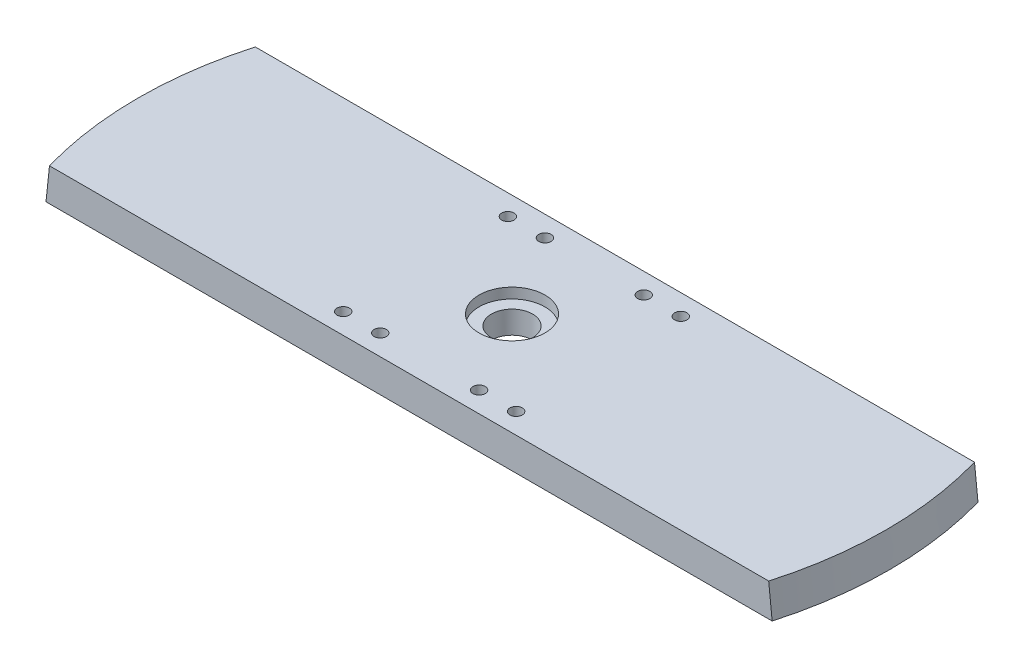
SolidWorks part; units mm, degrees
material "Acrylic (Medium-high impact)"
ref_plane "Front Plane" through (0, 0, 0) normal (0, 0, 1) x (1, 0, 0)
ref_plane "Top Plane" through (0, 0, 0) normal (0, 1, 0) x (1, 0, 0)
ref_plane "Right Plane" through (0, 0, 0) normal (1, 0, 0) x (0, 0, -1)
sketch "Chassi Outline Sketch" plane through (0, 0, 0) normal (0, 0, 1) x (1, 0, 0)
  line L0 (0, 0) -> (0, 128) construction
  line L1 (0, 0) -> (109.2209, 0) construction
  line L2 (91.6709, 0) -> (85.17, 64) construction
  line L3 (85.17, 64) -> (-85.17, 64) construction
  line L4 (85.17, 75.9083) -> (85.17, 0) construction
  line L5 (-91.6709, 0) -> (-85.17, 64) construction
  line L6 (0, 0) -> (-164.8351, 0) construction
  point P11 (0, 64)
  dimension "D1" = 5.8
  dimension "D2" = 85.17
  dimension "D3" = 64
  dimension "D4" = 183.3418
  dimension "D5" = 170.34
sketch "Chassi Outline Round Sketch" plane through (0, 0, 0) normal (0, 1, 0) x (1, 0, 0)
  circle A0 centre (0, 0) radius 91.6709 construction
sketch "Sketch3" plane through (0, 0, 0) normal (0, 0, 1) x (1, 0, 0)
  line L0 (90.8583, 8) -> (91.6709, 0)
  line L1 (-91.6709, 0) -> (91.6709, 0)
  line L2 (91.6709, 0) -> (85.17, 64) construction
  line L3 (-90.8583, 8) -> (90.8583, 8)
  line L4 (0, 0) -> (0, 128) construction
  line L5 (0, 0) -> (0, 94.8794) construction
  line L6 (-90.8583, 8) -> (-91.6709, 0)
  point P12 (0, 8)
  dimension "D1" = 8
extrude "Base Plate Boss-Extrude1" add sketch "Sketch3" along normal blind 25 and the other way blind 25
sketch "Sketch4" plane through (0, 0, 0) normal (0, 0, 1) x (1, 0, 0)
  line L0 (90.8583, 8) -> (91.6709, 0)
  line L1 (0, 0) -> (109.2209, 0) construction
  line L2 (91.6709, 8) -> (90.8583, 8)
  line L3 (91.6709, 0) -> (85.17, 64) construction
  line L4 (90.8583, 8) -> (-90.8583, 8) construction
  line L5 (91.6709, 8) -> (97.9209, 8)
  line L7 (91.6709, 0) -> (97.9209, 0)
  line L8 (97.9209, 8) -> (97.9209, 0)
revolve "Base Plate Chassi Rounding Cut-Revolve1" cut sketch "Sketch4" angle 360 about L0
sketch "Sketch5" plane through (0, 0, 0) normal (0, -1, 0) x (1, 0, 0)
  circle A0 centre (0, 0) radius 5
  dimension "D1" = 10
extrude "Shaft Cut-Extrude1" cut sketch "Sketch5" against normal up to surface (8 mm away) up to face at (0, 8, 0)
sketch "Sketch6" plane through (0, 8, 0) normal (0, 1, 0) x (1, 0, 0)
  circle A0 centre (0, 0) radius 8
  dimension "D1" = 16
extrude "Shaft Bearing Cut-Extrude2" cut sketch "Sketch6" against normal blind 2.5
sketch "Sketch7" plane through (0, 8, 0) normal (0, 1, 0) x (1, 0, 0)
  line L0 (0, 0) -> (25, 0) construction
  line L1 (0, 0) -> (109.2209, 0) construction
  line L2 (0, 0) -> (-25, 0) construction
  line L3 (0, 0) -> (-164.8351, 0) construction
  line L4 (25, 25) -> (25, -25) construction
  line L5 (87.3512, 25) -> (-87.3512, 25) construction
  line L6 (87.3512, -25) -> (-87.3512, -25) construction
  line L7 (-25, 25) -> (-25, -25) construction
  line L8 (17, 25) -> (17, -25) construction
  line L9 (-17, 25) -> (-17, -25) construction
  line L10 (-12, 20) -> (0, 0) construction
  line L11 (12, 20) -> (-12, 20) construction
  line L12 (12, 20) -> (12, -20) construction
  line L13 (12, -20) -> (-12, -20) construction
  line L14 (-12, 20) -> (-12, -20) construction
  line L15 (0, 0) -> (12, 20) construction
  line L16 (0, 0) -> (12, -20) construction
  line L17 (0, 0) -> (-12, -20) construction
  circle A0 centre (12, 20) radius 1.5
  circle A1 centre (-12, 20) radius 1.5
  circle A2 centre (-12, -20) radius 1.5
  circle A3 centre (12, -20) radius 1.5
  dimension "D6" = 3
  dimension "D1" = 50
  dimension "D2" = 8
  dimension "D3" = 8
  dimension "D4" = 5
  dimension "D5" = 5
extrude "Bearing Plate Mounting Holes Cut-Extrude3" cut sketch "Sketch7" against normal up to surface (8 mm away) up to face at (5, 0, 0)
sketch "Sketch8" plane through (0, 8, 0) normal (0, 1, 0) x (1, 0, 0)
  line L0 (0, 0) -> (25, 0) construction
  line L1 (0, 0) -> (109.2209, 0) construction
  line L2 (0, 0) -> (-25, 0) construction
  line L3 (0, 0) -> (-164.8351, 0) construction
  line L4 (25, 25) -> (25, -25) construction
  line L5 (87.3512, 25) -> (-87.3512, 25) construction
  line L6 (87.3512, -25) -> (-87.3512, -25) construction
  line L7 (-25, 25) -> (-25, -25) construction
  line L8 (17, 25) -> (17, -25) construction
  line L9 (-17, 25) -> (-17, -25) construction
  line L10 (-21, 20) -> (0, 0) construction
  line L11 (21, 20) -> (-21, 20) construction
  line L12 (21, 20) -> (21, -20) construction
  line L13 (21, -20) -> (-21, -20) construction
  line L14 (-21, 20) -> (-21, -20) construction
  line L15 (0, 0) -> (21, 20) construction
  line L16 (0, 0) -> (-21, -20) construction
  line L17 (0, 0) -> (21, -20) construction
  circle A0 centre (21, 20) radius 1.5
  circle A1 centre (-21, 20) radius 1.5
  circle A2 centre (-21, -20) radius 1.5
  circle A3 centre (21, -20) radius 1.5
  dimension "D6" = 3
  dimension "D1" = 50
  dimension "D2" = 8
  dimension "D3" = 8
  dimension "D4" = 4
  dimension "D5" = 5
extrude "Base Side Mounting Holes Cut-Extrude4" cut sketch "Sketch8" against normal up to surface (8 mm away) up to face at (13.5, 0, 20)
